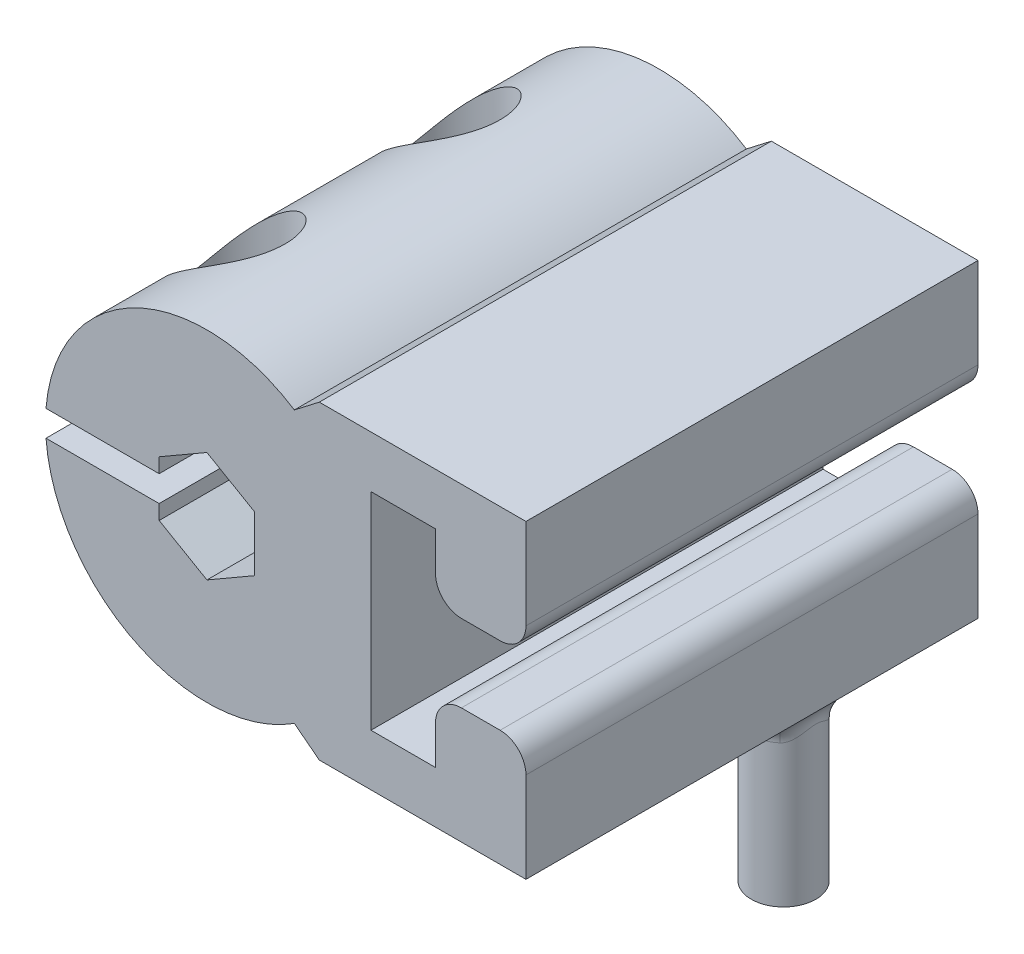
SolidWorks part; units mm, degrees
ref_plane "Front Plane" through (0, 0, 0) normal (0, 0, 1) x (1, 0, 0)
ref_plane "Top Plane" through (0, 0, 0) normal (0, 1, 0) x (1, 0, 0)
ref_plane "Right Plane" through (0, 0, 0) normal (1, 0, 0) x (0, 0, -1)
sketch "Sketch1" plane through (0, 0, 0) normal (0, 0, 1) x (1, 0, 0)
  line L0 (-20.2969, 1) -> (-3.7, 1)
  line L1 (-3.7, 2.1362) -> (-3.7, 1)
  line L2 (-3.7, -2.1362) -> (0, -4.2724)
  line L3 (0, -4.2724) -> (3.7, -2.1362)
  line L4 (3.7, -2.1362) -> (3.7, 2.1362)
  line L5 (3.7, 2.1362) -> (0, 4.2724)
  line L6 (0, 4.2724) -> (-3.7, 2.1362)
  line L7 (-3.7, 0) -> (-22.8855, 0) construction
  line L8 (-20.2969, -1) -> (-3.7, -1)
  line L9 (-20.2969, 1) -> (-20.2969, -1)
  line L10 (-3.7, -1) -> (-3.7, -2.1362)
  arc A0 (-1.85, -3.2043) -> (-1.85, 3.2043) centre (0, 0) ccw construction
  circle A1 centre (0, 0) radius 12.5
  dimension "D2" = 25
  dimension "D1" = 7.4
  dimension "D3" = 1
extrude "Boss-Extrude1" add sketch "Sketch1" along normal blind 35 contours L8 A1 L0 L1 L6 L5 L4 L3 L2 L10 region at (0.4863, 12.137, 0)
ref_plane "Plane1" through (0, 12.5, 0) normal (0, 1, 0) x (1, 0, 0)
sketch "Sketch2" plane through (0, 12.5, 0) normal (0, 1, 0) x (1, 0, 0)
  line L0 (-12.4599, 0) -> (-7.0788, -9.1755) construction
  line L1 (-7.0788, -9.1755) -> (-7.0788, -25.8245) construction
  line L2 (-7.0788, -25.8245) -> (-12.4599, -35) construction
  circle A0 centre (-7.0788, -9.1755) radius 1.8669
  circle A1 centre (-7.0788, -25.8245) radius 1.8669
  dimension "D1" = 3.7338
extrude "Cut-Extrude1" cut sketch "Sketch2" against normal through all
sketch "Sketch3" plane through (0, 12.5, 0) normal (0, 1, 0) x (1, 0, 0)
  circle A0 centre (-7.0788, -9.1755) radius 3.9497
  circle A1 centre (-7.0788, -25.8245) radius 3.9497
  dimension "D1" = 7.8994
extrude "Cut-Extrude2" cut sketch "Sketch3" against normal blind 8
ref_plane "Plane2" through (0, -12.5, 0) normal (0, -1, 0) x (-1, 0, 0)
sketch "Sketch4" plane through (0, -12.5, 0) normal (0, -1, 0) x (-1, 0, 0)
  line L1 (7.0788, -5.2307) -> (3.6625, -7.2031)
  line L2 (3.6625, -7.2031) -> (3.6625, -11.1479)
  line L3 (3.6625, -11.1479) -> (7.0788, -13.1203)
  line L4 (7.0788, -13.1203) -> (10.4951, -11.1479)
  line L5 (10.4951, -11.1479) -> (10.4951, -7.2031)
  line L6 (10.4951, -7.2031) -> (7.0788, -5.2307)
  line L7 (7.0788, -21.8797) -> (3.6625, -23.8521)
  line L8 (3.6625, -23.8521) -> (3.6625, -27.7969)
  line L9 (3.6625, -27.7969) -> (7.0788, -29.7693)
  line L10 (7.0788, -29.7693) -> (10.4951, -27.7969)
  line L11 (10.4951, -27.7969) -> (10.4951, -23.8521)
  line L12 (10.4951, -23.8521) -> (7.0788, -21.8797)
  circle A0 centre (7.0788, -9.1755) radius 3.4163 construction
  circle A1 centre (7.0788, -25.8245) radius 3.4163 construction
  dimension "D1" = 6.8326
extrude "Cut-Extrude3" cut sketch "Sketch4" against normal blind 8
sketch "Sketch5" plane through (0, 0, 0) normal (0, 0, -1) x (-1, 0, 0)
  line L0 (-8.7, 12) -> (-6.7683, 10.509)
  line L5 (-8.7, -12) -> (-6.7683, -10.509)
  line L6 (-17.7, 3) -> (-17.7, 8)
  line L19 (-8.7, -12) -> (-24.7, -12)
  line L21 (-8.7, 12) -> (-24.7, 12)
  line L22 (-24.7, -12) -> (-24.7, -3)
  line L23 (-12.7, -8) -> (-17.7, -8)
  line L24 (-12.7, -8) -> (-12.7, 8)
  line L25 (-12.7, 8) -> (-17.7, 8)
  line L26 (-17.7, -8) -> (-17.7, -3)
  line L27 (-17.7, -3) -> (-24.7, -3)
  line L29 (-17.7, 3) -> (-24.7, 3)
  line L31 (-24.7, 3) -> (-24.7, 12)
  line L34 (0, 12.5) -> (0, -12.5) construction
  arc A0 (12.4599, 1) -> (12.4599, -1) centre (0, 0) ccw construction
  arc A1 (-6.7683, 10.509) -> (-6.7683, -10.509) centre (0, 0) ccw
  dimension "D5" = 7
  dimension "D1" = 16
  dimension "D2" = 24
  dimension "D3" = 6
  dimension "D6" = 12
  dimension "D7" = 24.7
extrude "Boss-Extrude2" add sketch "Sketch5" against normal through all
fillet "Fillet1" radius 2 4 edges at (17.7, -3, 17.5) (17.7, 3, 17.5) (24.7, 3, 17.5) (24.7, -3, 17.5)
sketch "Sketch6" plane through (0, -12, 0) normal (0, -1, 0) x (1, 0, 0)
  circle A0 centre (21.7627, 12.1144) radius 2.5
  dimension "D1" = 5
extrude "Boss-Extrude3" add sketch "Sketch6" along normal blind 13
fillet "Fillet2" radius 2 1 edges at (21.7627, -12, 9.6144)
